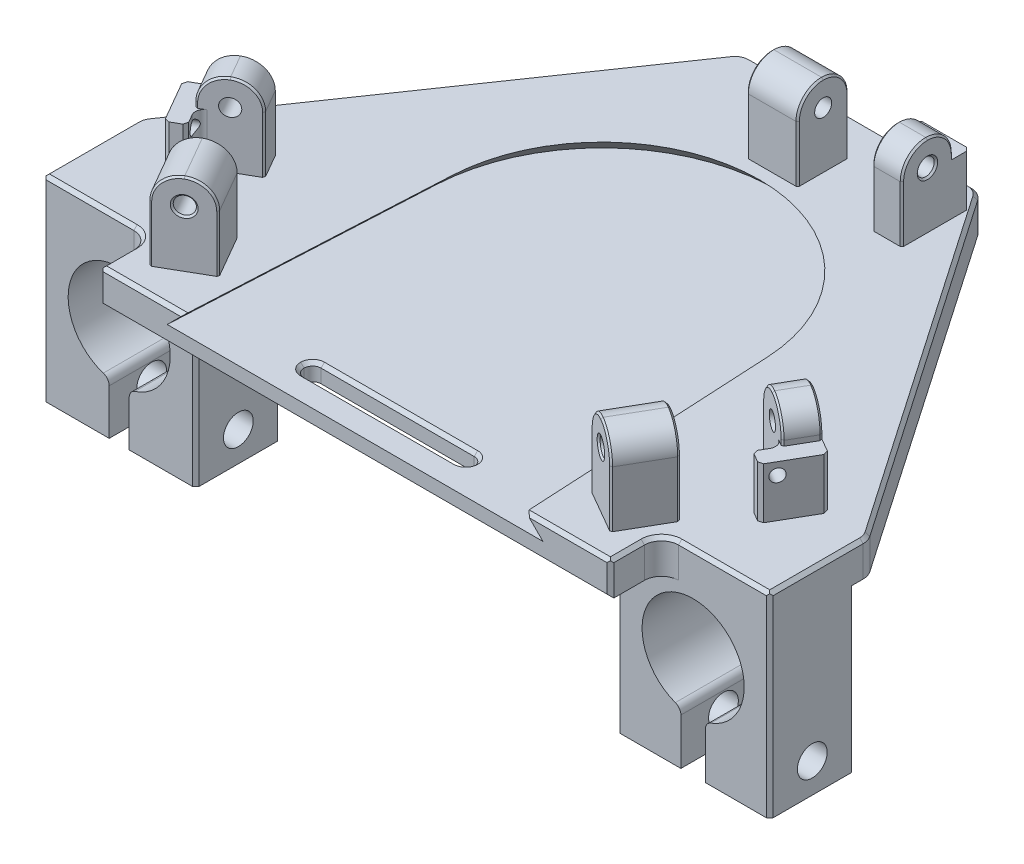
SolidWorks part; units mm, degrees
ref_plane "Front Plane" through (0, 0, 0) normal (0, 0, 1) x (1, 0, 0)
ref_plane "Top Plane" through (0, 0, 0) normal (0, 1, 0) x (1, 0, 0)
ref_plane "Right Plane" through (0, 0, 0) normal (1, 0, 0) x (0, 0, -1)
sketch "Sketch1" plane through (0, 0, 0) normal (0, 1, 0) x (1, 0, 0)
  circle A0 centre (0, 0) radius 20
  dimension "D1" = 40
extrude "Boss-Extrude1" add sketch "Sketch1" along normal mid plane 2
sketch "Sketch3" plane through (0, 1, 0) normal (0, 1, 0) x (1, 0, 0)
  line L0 (0, 0) -> (-12.9904, -7.5) construction
  line L1 (0, 0) -> (0, 15) construction
  line L2 (0, 0) -> (12.9904, -7.5) construction
  line L4 (-1.5, 16.5) -> (1.5, 16.5)
  line L5 (-1.5, 16.5) -> (-1.5, 13.5)
  line L6 (-1.5, 13.5) -> (1.5, 13.5)
  line L7 (1.5, 16.5) -> (1.5, 13.5)
  line L8 (-1.5, 16.5) -> (1.5, 13.5) construction
  line L9 (-1.5, 13.5) -> (1.5, 16.5) construction
  circle A0 centre (0, 0) radius 15 construction
  point P0 (0, 0)
  dimension "D1" = 30
  dimension "D2" = 120
  dimension "D3" = 120
  dimension "D4" = 3
  dimension "D5" = 3
extrude "Boss-Extrude2" add sketch "Sketch3" along normal blind 4.8
fillet "Fillet1" radius 1.5 2 edges at (0, 5.8, -16.5) (0, 5.8, -13.5)
ref_plane "Plane1" through (0, 0, 0) normal (-1, 0, 0) x (0, 0, 1)
sketch "Sketch4" plane through (0, 0, 0) normal (-1, 0, 0) x (0, 0, 1)
  line L1 (20, 1) -> (-20, 1) construction
  circle A0 centre (-15, 4.3) radius 0.5
  point P2 (-15, 5.8)
  dimension "D2" = 1
  dimension "D1" = 3.3
  dimension "D3" = 15
extrude "Cut-Extrude1" cut sketch "Sketch4" against normal through all and the other way through all
ref_axis "Axis1" through (0, 1, 0) along (0, -1, 0)
pattern_circular "CirPattern1" count 3 every 120 about axis through (0, 1, 0) along (0, -1, 0) of "Fillet1", "Boss-Extrude2", "Cut-Extrude1"
sketch "Sketch12" plane through (0, -1, 0) normal (0, -1, 0) x (1, 0, 0)
  line L0 (-12.3595, 6.25) -> (0, 6.25) construction
  line L1 (0, 6.25) -> (12.3595, 6.25) construction
  line L2 (0, 0) -> (0, -15) construction
  line L3 (0, 0) -> (12.9904, 7.5) construction
  line L8 (-2.55, -15) -> (2.55, -15) construction
  line L11 (0, -15) -> (0, -20) construction
  line L16 (-12.3595, 3) -> (-21.3595, 3)
  line L17 (-12.3595, 3) -> (-12.3595, 8)
  line L18 (-12.3595, 8) -> (-21.3595, 8)
  line L19 (-21.3595, 3) -> (-21.3595, 8)
  line L22 (12.3595, 3) -> (21.3595, 3)
  line L23 (12.3595, 3) -> (12.3595, 8)
  line L24 (12.3595, 8) -> (21.3595, 8)
  line L25 (21.3595, 3) -> (21.3595, 8)
  line L28 (3, -18.75) -> (-6, -18.75)
  line L29 (3, -18.75) -> (3, -13.75)
  line L30 (3, -13.75) -> (-6, -13.75)
  line L31 (-6, -18.75) -> (-6, -13.75)
  point P29 (-1.5, -17)
  dimension "D2" = 6.25
  dimension "D3" = 5
  dimension "D4" = 15
  dimension "D5" = 120
  dimension "D6" = 1.5
  dimension "D7" = 9
  dimension "D8" = 5
  dimension "D9" = 12.3595
  dimension "D10" = 1.75
  dimension "D11" = 1.25
  dimension "D12" = 15
  dimension "D13" = 3
ref_plane "Plane2" through (0, 0, 0) normal (0.5, 0, 0.866) x (0.866, 0, -0.5)
ref_plane "Plane3" through (0, 0, 0) normal (-0.5, 0, 0.866) x (0.866, 0, 0.5)
sketch "Sketch14" plane through (0, 1, 0) normal (0, 1, 0) x (1, 0, 0)
  line L0 (0, 20) -> (0, 3.4501) construction
  line L1 (-20, 0) -> (-23.8068, -4.7152)
  line L2 (-23.8068, -4.7152) -> (-23.8068, -8.7192)
  line L3 (-23.8068, -8.7192) -> (-12.9912, -15.2062)
  line L4 (23.8068, -8.7192) -> (12.9912, -15.2062)
  line L5 (23.8068, -4.7152) -> (23.8068, -8.7192)
  line L6 (20, 0) -> (23.8068, -4.7152)
  arc A0 (20, 0) -> (12.9912, -15.2062) centre (0, 0) cw
  circle A1 centre (0, 0) radius 20 construction
  arc A2 (-20, 0) -> (-12.9912, -15.2062) centre (0, 0) ccw
extrude "Boss-Extrude6" add sketch "Sketch14" against normal up to surface (2 mm away) up to face at (0, -1, 20)
sketch "Sketch35" plane through (0, 1, 0) normal (0, 1, 0) x (1, 0, 0)
  line L0 (-20, 0) -> (-8.7191, 17.9994)
  line L1 (8.7191, 17.9994) -> (20, 0)
  line L2 (23.8068, -4.7152) -> (20, 0) construction
  arc A2 (-20, 0) -> (-8.7191, 17.9994) centre (-7.7658, 4.8671) cw
  arc A3 (8.7191, 17.9994) -> (20, 0) centre (8.7167, 5.4631) cw
  arc A6 (20, 0) -> (-20, 0) centre (0, 0) ccw construction
  arc A7 (20, 0) -> (-20, 0) centre (0, 0) ccw construction
extrude "Cut-Extrude15" cut sketch "Sketch35" against normal blind 27
fillet "Fillet28" radius 5 2 edges at (8.7191, 0, -17.9994) (-8.7191, 0, -17.9994)
fillet "Fillet30" radius 5 6 edges at (20, 0, 0) (-20, 0, 0) (-23.8068, 0, 8.7192) (-23.8068, 0, 4.7152) (23.8068, 0, 8.7192) (23.8068, 0, 4.7152)
extrude "Boss-Extrude11" add sketch "Sketch12" along normal blind 9.5
sketch "Sketch36" plane through (0, 0, 3) normal (0, 0, -1) x (-1, 0, 0)
  line L0 (-21.3595, -1) -> (-12.3595, -10.5) construction
  line L1 (-12.3595, -10.5) -> (-12.3595, -1) construction
  line L2 (-12.3595, -1) -> (-21.3595, -10.5) construction
  line L3 (21.3595, -1) -> (12.3595, -10.5) construction
  line L4 (12.3595, -1) -> (21.3595, -10.5) construction
  line L5 (-12.3595, -10.5) -> (-21.3595, -10.5) construction
  line L6 (-12.3595, -1) -> (-21.3595, -1) construction
  line L7 (6, -10.5) -> (-3, -10.5) construction
  circle A0 centre (-16.8595, -4.5) radius 3
  circle A1 centre (16.8595, -4.5) radius 3
  circle A2 centre (1.5, -4.5) radius 3
  point P7 (1.5, -10.5)
  point P8 (-16.8595, -5.75)
  point P23 (16.8595, -5.75)
  dimension "D1" = 6
  dimension "D2" = 3.5
extrude "Cut-Extrude16" cut sketch "Sketch36" against normal mid plane 81
sketch "Sketch41" plane through (0, 1, 0) normal (0, 1, 0) x (1, 0, 0)
  line L0 (1.5, 16.5) -> (-1.5, 16.5) construction
  line L1 (5.875, 16.5) -> (7.625, 16.5)
  line L2 (5.875, 16.5) -> (5.875, 13.5)
  line L3 (5.875, 13.5) -> (7.625, 13.5)
  line L4 (7.625, 16.5) -> (7.625, 13.5)
  line L5 (5.875, 16.5) -> (7.625, 13.5) construction
  line L6 (5.875, 13.5) -> (7.625, 16.5) construction
  line L7 (-1.5, 13.5) -> (1.5, 13.5) construction
  line L8 (1.5, 13.5) -> (1.5, 16.5) construction
  line L9 (15.5038, -0.1466) -> (18.1019, -1.6466)
  line L10 (15.5038, -0.1466) -> (14.6288, -1.6621)
  line L11 (18.1019, -1.6466) -> (17.2269, -3.1621)
  line L12 (14.6288, -1.6621) -> (17.2269, -3.1621)
  line L13 (15.5038, -0.1466) -> (17.2269, -3.1621) construction
  line L14 (18.1019, -1.6466) -> (14.6288, -1.6621) construction
  line L15 (13.5394, -9.549) -> (15.0394, -6.951) construction
  line L16 (12.4413, -5.451) -> (10.9413, -8.049) construction
  line L17 (1.5, 15) -> (6.75, 15) construction
  line L18 (13.7404, -6.201) -> (16.3654, -1.6543) construction
  line L19 (15.0394, -6.951) -> (13.7404, -6.201) construction
  line L20 (-14.6288, -1.6621) -> (-15.5038, -0.1466)
  line L21 (-14.6288, -1.6621) -> (-17.2269, -3.1621)
  line L22 (-15.5038, -0.1466) -> (-18.1019, -1.6466)
  line L23 (-17.2269, -3.1621) -> (-18.1019, -1.6466)
  line L24 (-14.6288, -1.6621) -> (-18.1019, -1.6466) construction
  line L25 (-15.5038, -0.1466) -> (-17.2269, -3.1621) construction
  line L26 (-12.4413, -5.451) -> (-13.7404, -6.201) construction
  line L27 (-10.9413, -8.049) -> (-12.4413, -5.451) construction
  line L28 (-15.0394, -6.951) -> (-13.5394, -9.549) construction
  line L30 (-16.3654, -1.6543) -> (-13.7404, -6.201) construction
  line L31 (-12.4413, -5.451) -> (-15.0394, -6.951) construction
  point P0 (6.75, 15)
  point P13 (16.3654, -1.6543)
  point P29 (-16.3654, -1.6543)
  dimension "D2" = 1.75
  dimension "D4" = 5.25
extrude "Boss-Extrude12" add sketch "Sketch41" along normal blind 4.8
sketch "Sketch48" plane through (0, 0, -16.5) normal (0, 0, -1) x (-1, 0, 0)
  line L0 (-7.625, 5.8) -> (-7.625, 1) construction
  line L1 (-7.625, 1) -> (-4.625, 1)
  line L2 (-7.625, 1) -> (-7.625, 4)
  line L3 (-7.625, 4) -> (-4.625, 4)
  line L4 (-4.625, 1) -> (-4.625, 4)
  line L5 (-7.625, 1) -> (-5.875, 1) construction
  dimension "D1" = 3
  dimension "D2" = 3
extrude "Boss-Extrude13" add sketch "Sketch48" along normal blind 1 contours L4 L3 L2 L1
sketch "Sketch49" plane through (14.2894, 0, 8.25) normal (0.866, 0, 0.5) x (0.5, 0, -0.866)
  line L1 (7.625, 1) -> (4.625, 1)
  line L2 (7.625, 1) -> (7.625, 4)
  line L3 (7.625, 4) -> (4.625, 4)
  line L4 (4.625, 1) -> (4.625, 4)
  dimension "D1" = 3
  dimension "D2" = 3
extrude "Boss-Extrude14" add sketch "Sketch49" along normal blind 1
sketch "Sketch50" plane through (-14.2894, 0, 8.25) normal (-0.866, 0, 0.5) x (0.5, 0, 0.866)
  line L1 (-7.625, 1) -> (-4.625, 1)
  line L2 (-7.625, 1) -> (-7.625, 4)
  line L3 (-7.625, 4) -> (-4.625, 4)
  line L4 (-4.625, 1) -> (-4.625, 4)
  dimension "D1" = 3
  dimension "D2" = 3
extrude "Boss-Extrude15" add sketch "Sketch50" along normal blind 1
fillet "Fillet47" radius 1.5 6 edges at (6.75, 5.8, -16.5) (6.75, 5.8, -13.5) (15.0663, 5.8, 0.9043) (17.6644, 5.8, 2.4043) (-15.0663, 5.8, 0.9043) (-17.6644, 5.8, 2.4043)
sketch "Sketch42" plane through (5.875, 0, 0) normal (-1, 0, 0) x (0, 0, 1)
  circle A0 centre (-15, 4.3) radius 0.5
  circle A1 centre (-15, 4.3) radius 0.5 construction
extrude "Cut-Extrude20" cut sketch "Sketch42" against normal blind 10
sketch "Sketch43" plane through (-2.9375, 0, -5.0879) normal (0.5, 0, 0.866) x (0.866, 0, -0.5)
  circle A0 centre (-15, 4.3) radius 0.5
  circle A1 centre (-15, 4.3) radius 0.5 construction
extrude "Cut-Extrude21" cut sketch "Sketch43" against normal blind 10
sketch "Sketch44" plane through (2.9375, 0, -5.0879) normal (-0.5, 0, 0.866) x (0.866, 0, 0.5)
  circle A0 centre (15, 4.3) radius 0.5
  circle A1 centre (15, 4.3) radius 0.5 construction
extrude "Cut-Extrude22" cut sketch "Sketch44" against normal blind 10
sketch "Sketch45" plane through (0, 1, 0) normal (0, 1, 0) x (1, 0, 0)
  line L0 (0, 15) -> (0, 21.25) construction
  line L1 (-1.5, 15) -> (1.5, 15) construction
  line L2 (-12.9904, -7.5) -> (-18.403, -10.625) construction
  line L3 (-12.2404, -8.799) -> (-13.7404, -6.201) construction
  line L4 (12.9904, -7.5) -> (18.403, -10.625) construction
  line L5 (13.7404, -6.201) -> (12.2404, -8.799) construction
  dimension "D1" = 6.25
sketch "Sketch46" plane through (-21.3595, 0, 0) normal (-1, 0, 0) x (0, 0, 1)
  line L0 (8, -10.5) -> (3, -10.5) construction
  line L1 (-13.75, -10.5) -> (-18.75, -10.5) construction
  circle A0 centre (5.5, -8.75) radius 0.875
  circle A1 centre (-16.25, -8.75) radius 0.875
  point P2 (5.5, -10.5)
  point P3 (-16.25, -10.5)
  dimension "D1" = 1.75
  dimension "D2" = 1.75
extrude "Cut-Extrude23" cut sketch "Sketch46" against normal through all
sketch "Sketch47" plane through (0, 0, 8) normal (0, 0, 1) x (1, 0, 0)
  line L0 (-12.3595, -10.5) -> (-21.3595, -10.5) construction
  line L1 (-17.4478, -15.873) -> (-16.2713, -15.873)
  line L2 (-17.4478, -15.873) -> (-17.4478, -5.127)
  line L3 (-17.4478, -5.127) -> (-16.2713, -5.127)
  line L4 (-16.2713, -15.873) -> (-16.2713, -5.127)
  line L5 (-17.4478, -15.873) -> (-16.2713, -5.127) construction
  line L6 (-17.4478, -5.127) -> (-16.2713, -15.873) construction
  line L7 (3, -10.5) -> (-6, -10.5) construction
  line L8 (-2.1849, -15.873) -> (-0.8151, -15.873)
  line L9 (-2.1849, -15.873) -> (-2.1849, -5.127)
  line L10 (-2.1849, -5.127) -> (-0.8151, -5.127)
  line L11 (-0.8151, -15.873) -> (-0.8151, -5.127)
  line L12 (-2.1849, -15.873) -> (-0.8151, -5.127) construction
  line L13 (-2.1849, -5.127) -> (-0.8151, -15.873) construction
  line L14 (21.3595, -10.5) -> (12.3595, -10.5) construction
  line L15 (16.1409, -15.873) -> (17.5782, -15.873)
  line L16 (16.1409, -15.873) -> (16.1409, -5.127)
  line L17 (16.1409, -5.127) -> (17.5782, -5.127)
  line L18 (17.5782, -15.873) -> (17.5782, -5.127)
  line L19 (16.1409, -15.873) -> (17.5782, -5.127) construction
  line L20 (16.1409, -5.127) -> (17.5782, -15.873) construction
  point P0 (-16.8595, -10.5)
  point P7 (-1.5, -10.5)
  point P14 (16.8595, -10.5)
extrude "Cut-Extrude24" cut sketch "Sketch47" against normal through all
fillet "Fillet48" radius 0.5 3 edges at (17.2269, 2.5, 3.1621) (5.875, 2.5, -16.5) (-17.2269, 2.5, 3.1621)
sketch "Sketch51" plane through (-15.1554, 0, 8.75) normal (-0.866, 0, 0.5) x (0.5, 0, 0.866)
  line L0 (-4.625, 4) -> (-7.625, 4) construction
  line L1 (-4.625, 1) -> (-4.625, 4) construction
  circle A0 centre (-5.425, 3.3) radius 0.375
  dimension "D1" = 0.75
  dimension "D2" = 0.7
  dimension ".7" = 0.8
extrude "Cut-Extrude25" cut sketch "Sketch51" against normal blind 10.5
sketch "Sketch52" plane through (0, 0, -17.5) normal (0, 0, -1) x (-1, 0, 0)
  line L0 (-4.625, 1) -> (-4.625, 4) construction
  line L1 (-7.625, 4) -> (-4.625, 4) construction
  circle A0 centre (-5.425, 3.3) radius 0.375
  dimension "D1" = 0.75
  dimension "D2" = 0.8
  dimension "D3" = 0.7
sketch "Sketch53" plane through (15.1554, 0, 8.75) normal (0.866, 0, 0.5) x (0.5, 0, -0.866)
  line L1 (7.625, 4) -> (4.625, 4) construction
  line L2 (4.625, 4) -> (4.625, 1) construction
  circle A0 centre (5.425, 3.3) radius 0.375
  dimension "D3" = 0.75
  dimension "D1" = 0.7
  dimension "D2" = 0.8
extrude "Cut-Extrude26" cut sketch "Sketch53" against normal blind 10.5 contours A0
extrude "Cut-Extrude27" cut sketch "Sketch52" against normal blind 10.5 contours A0
chamfer "Chamfer1" distance 0.1 angle 45 24 edges at (-1.5, 2.65, -16.5) (-1.5, 5.3607, -16.0607) (-1.5, 5.3607, -13.9393) (-1.5, 2.65, -13.5) (1.5, 2.65, -16.5) (1.5, 5.3607, -16.0607) (1.5, 5.3607, -13.9393) (1.5, 2.65, -13.5) (12.4413, 2.65, 5.451) (12.8218, 5.3607, 5.6706) (15.0394, 2.65, 6.951) (14.6589, 5.3607, 6.7313) (10.9413, 2.65, 8.049) (11.3218, 5.3607, 8.2687) (13.1589, 5.3607, 9.3294) (13.5394, 2.65, 9.549) (-12.4413, 2.65, 5.451) (-15.0394, 2.65, 6.951) (-12.8218, 5.3607, 5.6706) (-14.6589, 5.3607, 6.7313) (-10.9413, 2.65, 8.049) (-11.3218, 5.3607, 8.2687) (-13.1589, 5.3607, 9.3294) (-13.5394, 2.65, 9.549)
chamfer "Chamfer2" distance 0.1 angle 45 24 edges at (-15.5038, 2.65, 0.1466) (-18.1019, 4.15, 1.6466) (-15.8843, 5.3607, 0.3662) (-17.7214, 5.3607, 1.4269) (-14.6288, 2.65, 1.6621) (-15.0093, 5.3607, 1.8818) (-17.2269, 4.15, 3.1621) (-16.8464, 5.3607, 2.9424) (5.875, 4.15, -16.5) (5.875, 2.65, -13.5) (5.875, 5.3607, -16.0607) (5.875, 5.3607, -13.9393) (7.625, 4.15, -16.5) (7.625, 5.3607, -16.0607) (7.625, 2.65, -13.5) (7.625, 5.3607, -13.9393) (15.5038, 2.65, 0.1466) (15.8843, 5.3607, 0.3662) (18.1019, 4.15, 1.6466) (17.7214, 5.3607, 1.4269) (14.6288, 2.65, 1.6621) (17.2269, 4.15, 3.1621) (15.0093, 5.3607, 1.8818) (16.8464, 5.3607, 2.9424)
ref_plane "Plane4" through (0, 0, 20) normal (0, 0, 1) x (1, 0, 0)
sketch "Sketch54" plane through (0, 0, 20) normal (0, 0, 1) x (1, 0, 0)
  line L1 (-26.8974, -6.8874) -> (26.8974, -6.8874)
  line L2 (-26.8974, -6.8874) -> (-26.8974, 6.8874)
  line L3 (-26.8974, 6.8874) -> (26.8974, 6.8874)
  line L4 (26.8974, -6.8874) -> (26.8974, 6.8874)
  line L5 (-26.8974, -6.8874) -> (26.8974, 6.8874) construction
  line L6 (-26.8974, 6.8874) -> (26.8974, -6.8874) construction
  point P0 (0, 0)
extrude "Cut-Extrude28" cut sketch "Sketch54" against normal blind 9
sketch "Sketch55" plane through (0, 1, 0) normal (0, 1, 0) x (1, 0, 0)
  line L0 (-10.0353, -11) -> (-9.25, 3.9848)
  line L1 (20.0041, -11) -> (-20.0041, -11) construction
  line L2 (9.25, 3.9848) -> (10.0353, -11)
  line L3 (0, -11) -> (-10.0353, -11) construction
  line L4 (0, -11) -> (10.0353, -11) construction
  line L5 (-10.0353, -11) -> (10.0353, -11)
  arc A0 (-9.25, 3.9848) -> (9.25, 3.9848) centre (0, 3.5) cw
  dimension "D1" = 87
  dimension "D2" = 87
  dimension "D4" = 9.25
  dimension "D5" = 3.5
extrude "Cut-Extrude29" cut sketch "Sketch55" against normal blind 1 draft 45 draft outward yes
chamfer "Chamfer3" distance 0.1 angle 45 6 edges at (-12.6734, 4.3, 9.049) (-16.3699, 4.3, 0.6466) (-1.5, 4.3, -15.5) (7.625, 4.3, -14.5) (17.2359, 4.3, 1.1466) (11.8074, 4.3, 8.549)
fillet "Fillet49" radius 0.5 6 edges at (-17.4478, -7.4418, 5.5) (-0.8151, -7.4208, -16.25) (-16.2713, -7.4418, 5.5) (-2.1849, -7.4208, -16.25) (16.1409, -7.4127, 5.5) (17.5782, -7.4127, 5.5)
sketch "Sketch57" plane through (0, -1, 0) normal (0, -1, 0) x (1, 0, 0)
  line L0 (-15, 11) -> (-15, 8)
  line L1 (20.0041, 11) -> (-20.0041, 11) construction
  line L2 (-15, 8) -> (-21.3595, 8)
  line L3 (-21.3595, 8) -> (-21.3595, 2.2)
  line L4 (-21.3595, 2.2) -> (-6.9597, -18.75)
  line L6 (-15, 11) -> (15, 11)
  line L7 (15, 11) -> (15, 8)
  line L8 (21.3595, 8) -> (12.3595, 8) construction
  line L9 (15, 8) -> (21.3595, 8)
  line L10 (21.3595, 8) -> (21.3595, 2.2)
  line L11 (21.3595, 3) -> (21.3595, 8) construction
  line L12 (6.9597, -18.75) -> (21.3595, 2.2)
  line L14 (-21.3595, 8) -> (-21.3595, 3) construction
  line L18 (21.3595, 3) -> (21.3595, 8) construction
  line L19 (-17.4478, 8) -> (-21.3595, 8) construction
  line L21 (-6.9597, -18.75) -> (6.9597, -18.75)
  line L23 (-6, -18.75) -> (-2.1849, -18.75) construction
  arc A2 (-7.0745, -18.707) -> (7.0745, -18.707) centre (0, 0) ccw construction
  dimension "D1" = 15
  dimension "D2" = 15
  dimension "D3" = 5.8
extrude "Cut-Extrude31" cut sketch "Sketch57" against normal blind 3 flip side to cut
sketch "Sketch56" plane through (0, 0, 0) normal (0, 1, 0) x (1, 0, 0)
  line L1 (-5, -8.5) -> (5, -8.5)
  line L2 (-5, -8.5) -> (-5, -9.5)
  line L3 (-5, -9.5) -> (5, -9.5)
  line L4 (5, -8.5) -> (5, -9.5)
  line L5 (-5, -8.5) -> (5, -9.5) construction
  line L6 (-5, -9.5) -> (5, -8.5) construction
  point P0 (0, -9)
  dimension "D1" = 1
  dimension "D2" = 8.5
  dimension "D3" = 10
extrude "Cut-Extrude30" cut sketch "Sketch56" against normal blind 3
fillet "Fillet50" radius 0.5 4 edges at (5, -0.5, 9.5) (5, -0.5, 8.5) (-5, -0.5, 8.5) (-5, -0.5, 9.5)
chamfer "Chamfer5" distance 0.2 angle 45 9 edges at (-18.9679, 2.5, 2.1466) (18.9679, 2.5, 2.1466) (7.625, 2.5, -17.5) (4.625, 2.5, -17.5) (4.625, 2.5, -16.5) (16.6019, 2.5, 4.2446) (17.4679, 2.5, 4.7446) (-16.6019, 2.5, 4.2446) (-17.4679, 2.5, 4.7446)
fillet "Fillet51" radius 1 2 edges at (-15, 0, 8) (15, 0, 8)
chamfer "Chamfer4" distance 0.2 angle 45 12 edges at (3, -5.75, -18.75) (3, -5.75, -13.75) (-6, -5.75, -18.75) (-6, -5.75, -13.75) (-21.3595, -5.75, 3) (-21.3595, -4.75, 8) (-12.3595, -5.75, 3) (-12.3595, -5.75, 8) (12.3595, -5.75, 3) (21.3595, -5.75, 3) (21.3595, -4.75, 8) (12.3595, -5.75, 8)
chamfer "Chamfer7" distance 0.2 angle 45 2 edges at (15, 0, 11) (-15, 0, 11)
fillet "Fillet52" radius 1 4 edges at (-21.3595, 0, 2.2) (21.3595, 0, 2.2) (6.9597, 0, -18.75) (-6.9597, 0, -18.75)
chamfer "Chamfer6" distance 0.2 angle 45 24 edges at (0, 0, 8.5) (-4.8536, 0, 8.6464) (4.8536, 0, 8.6464) (-4.8536, 0, 9.3536) (4.8536, 0, 9.3536) (0, 0, 9.5) (0, -1, 11) (12.4177, 1, 11) (-12.4177, 1, 11) (15, 1, 9.9) (15.2929, 1, 8.2929) (18.5798, 1, 8) (21.3595, 1, 5.1553) (21.3146, 1, 2.214) (14.2207, 1, -8.1862) (6.8992, 1, -18.635) (0, 1, -18.75) (-6.8992, 1, -18.635) (-14.2207, 1, -8.1862) (-21.3146, 1, 2.214) (-21.3595, 1, 5.1553) (-18.5798, 1, 8) (-15, 1, 9.9) (-15.2929, 1, 8.2929)
ref_axis "Axis2" through (31.3037, 4.3, -15) along (-1, 0, 0)
ref_axis "Axis3" through (12.6529, 4.3, 8.0846) along (0.5, 0, -0.866)
ref_point "Point1"
ref_point "Point2"
ref_point "Point4"
ref_axis "Axis4" through (0.05, 4.3, -15) along (0.5, 0, 0.866)
